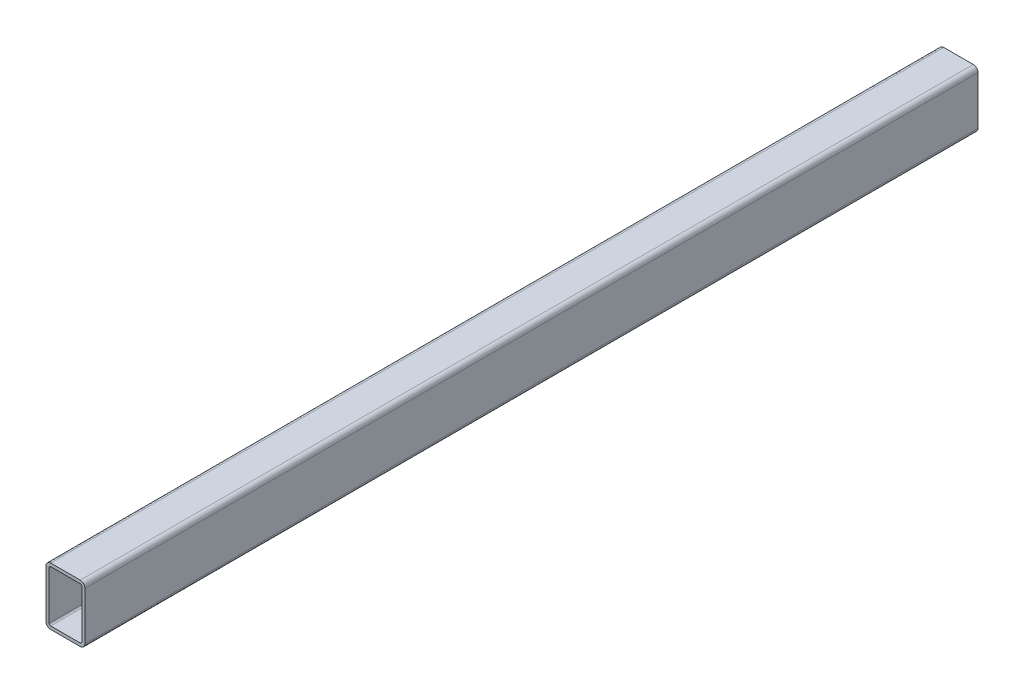
SolidWorks part; units mm, degrees
material "Alloy Steel"
ref_plane "Front" through (0, 0, 0) normal (0, 0, 1) x (1, 0, 0)
ref_plane "Top" through (0, 0, 0) normal (0, 1, 0) x (1, 0, 0)
ref_plane "Right" through (0, 0, 0) normal (1, 0, 0) x (0, 0, -1)
sketch "Sketch1" plane through (0, 0, 0) normal (0, 0, 1) x (1, 0, 0)
  line L0 (0, 40.8909) -> (0, -24.1212) construction
  line L1 (-9.5, 37) -> (9.5, 37)
  line L2 (-12.5, 34) -> (-12.5, 3)
  line L3 (-9.5, 0) -> (9.5, 0)
  line L4 (12.5, 34) -> (12.5, 3)
  arc A0 (-12.5, 3) -> (-9.5, 0) centre (-9.5, 3) ccw
  arc A1 (9.5, 0) -> (12.5, 3) centre (9.5, 3) ccw
  arc A2 (9.5, 37) -> (12.5, 34) centre (9.5, 34) cw
  arc A3 (-9.5, 37) -> (-12.5, 34) centre (-9.5, 34) ccw
  point P9 (-12.5, 0)
  point P12 (12.5, 0)
  point P15 (12.5, 37)
  dimension "D3" = 3
  dimension "D1" = 37
  dimension "D2" = 25
extrude "Extrude-Thin1" add sketch "Sketch1" along normal mid plane 574 thin contours L1 A2 L4 A1 L3 A0 L2 A3 thin type one direction reverse wall 2
